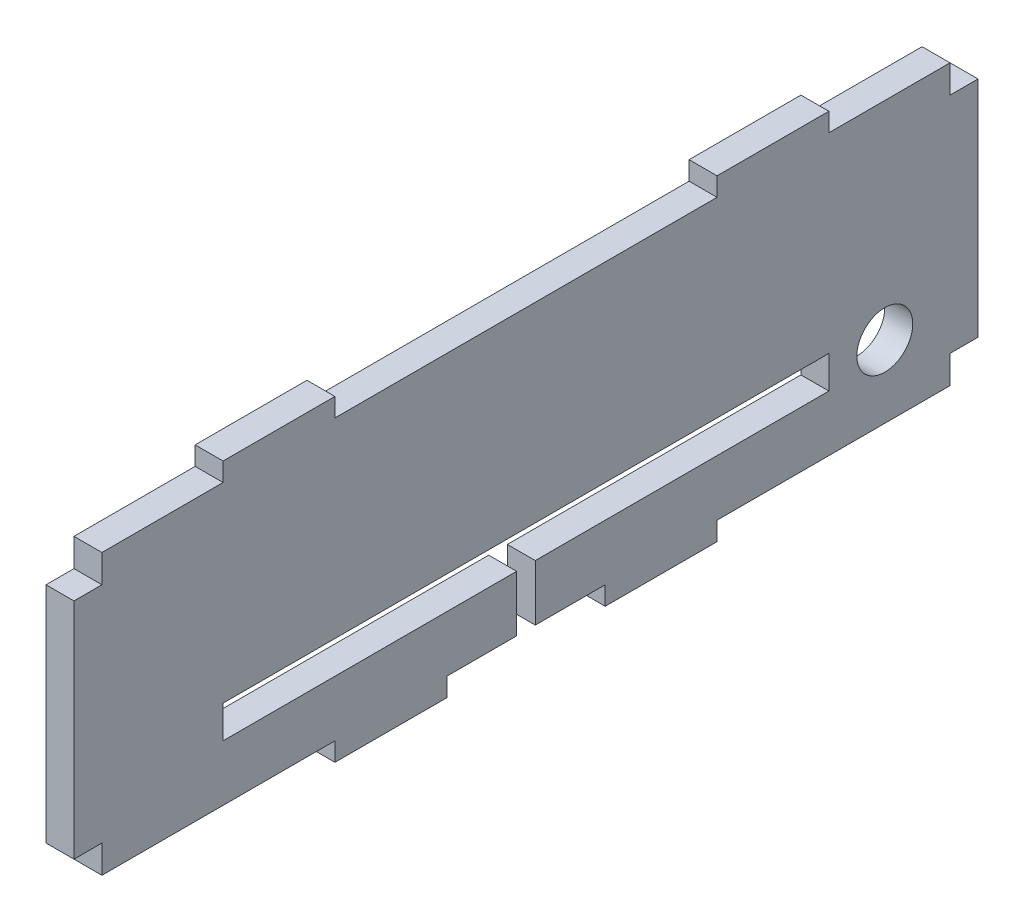
SolidWorks part; units mm, degrees
ref_plane "Front Plane" through (0, 0, 0) normal (0, 0, 1) x (1, 0, 0)
ref_plane "Top Plane" through (0, 0, 0) normal (0, 1, 0) x (1, 0, 0)
ref_plane "Right Plane" through (0, 0, 0) normal (1, 0, 0) x (0, 0, -1)
sketch "Sketch1" plane through (0, 0, 0) normal (1, 0, 0) x (0, 0, -1)
  line L0 (0, 0) -> (0, -32841.5669)
  line L1 (0, 0) -> (32841.5669, 0)
  line L2 (0, 5) -> (3, 5)
  line L3 (0, 0) -> (97, 0)
  line L4 (0, 0) -> (0, 34)
  line L5 (0, 34) -> (97, 34)
  line L6 (97, 0) -> (97, 34)
  line L11 (3, 5) -> (3, 2)
  line L12 (3, 2) -> (28, 2)
  line L13 (28, 2) -> (28, 0)
  line L14 (28, 0) -> (40, 0)
  line L15 (40, 0) -> (40, 2)
  line L16 (16, 8) -> (47.5, 8)
  line L17 (47.5, 8) -> (47.5, 2)
  line L18 (47.5, 2) -> (40, 2)
  line L19 (16, 8) -> (16, 11.5)
  line L20 (16, 11.5) -> (81, 11.5)
  line L21 (81, 11.5) -> (81, 8)
  line L22 (81, 8) -> (49.5, 8)
  line L23 (49.5, 8) -> (49.5, 2)
  line L24 (49.5, 2) -> (57, 2)
  line L25 (57, 2) -> (57, 0)
  line L26 (57, 0) -> (69, 0)
  line L27 (69, 0) -> (69, 2)
  line L28 (69, 2) -> (94, 2)
  line L29 (94, 2) -> (94, 5)
  line L30 (94, 5) -> (97, 5)
  line L31 (0, 29) -> (3, 29)
  line L32 (3, 29) -> (3, 32)
  line L33 (3, 32) -> (16, 32)
  line L34 (16, 32) -> (16, 34)
  line L35 (16, 34) -> (28, 34)
  line L36 (28, 34) -> (28, 32)
  line L37 (28, 32) -> (69, 32)
  line L38 (69, 32) -> (69, 34)
  line L39 (69, 34) -> (81, 34)
  line L40 (81, 34) -> (81, 32)
  line L41 (81, 32) -> (94, 32)
  line L42 (94, 32) -> (94, 29)
  line L43 (94, 29) -> (97, 29)
  circle A0 centre (87, 9.75) radius 3
  point P45 (0, 0)
  point P46 (81, 9.75)
  dimension "D12" = 7
  dimension "D1" = 34
  dimension "D2" = 97
  dimension "D3" = 2
  dimension "D4" = 3
  dimension "D5" = 3
  dimension "D6" = 2
  dimension "D7" = 12
  dimension "D8" = 17
  dimension "D9" = 3
  dimension "D10" = 3
  dimension "D11" = 12
  dimension "D13" = 12
  dimension "D14" = 2
  dimension "D15" = 2
  dimension "D16" = 12
  dimension "D17" = 2
  dimension "D18" = 3
  dimension "D19" = 5
  dimension "D20" = 3
  dimension "D21" = 12
  dimension "D22" = 12
  dimension "D23" = 3.5
  dimension "D24" = 6
extrude "Boss-Extrude1" add sketch "Sketch1" along normal blind 3 contours L43 L42 L41 L40 L5 L38 L37 L36 L34 L33 L32 L31 L4 L2 L11 L12 L13 L3 L15 L18 L17 L16 L19 L20 L21 L22 L23 L24 L25 L27 L28 L29 L30 L6 region at (0, 17.7395, -48.0972)
